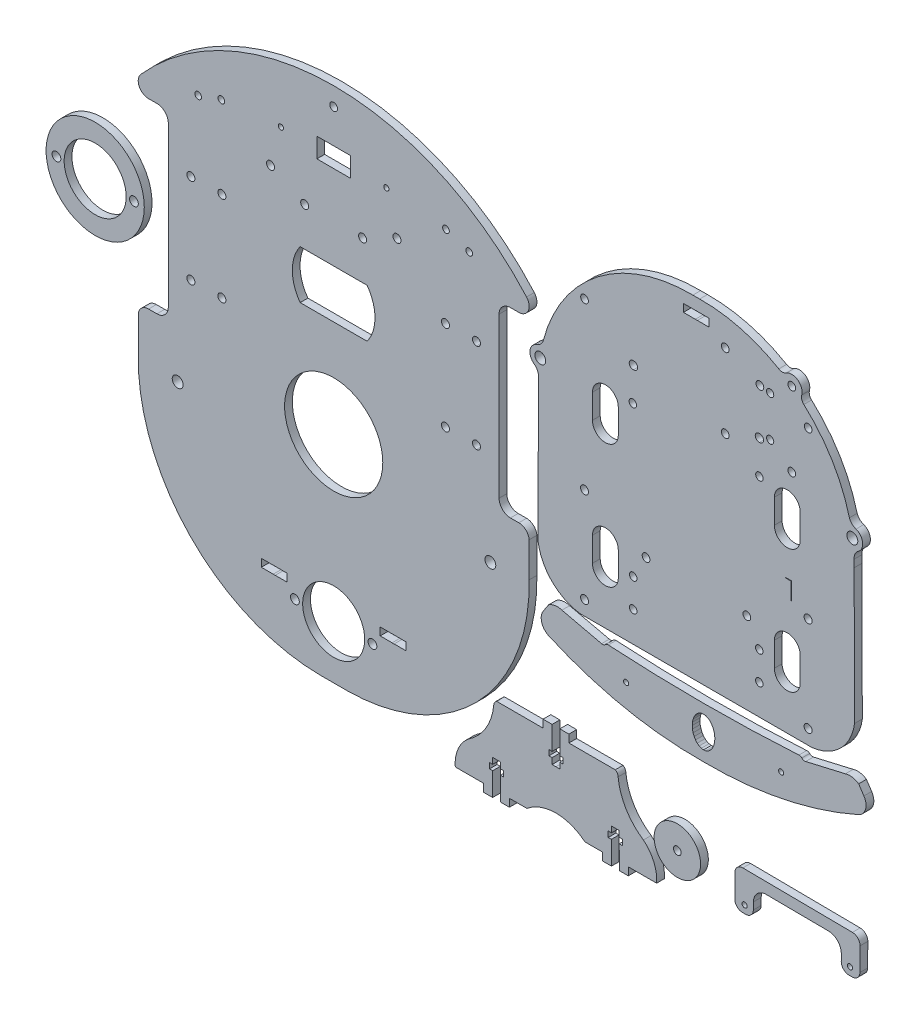
SolidWorks part; units mm, degrees
other "caster_spacer"
other "bottom_plate"
other "top_plate"
other "bumper"
other "rear_upright"
other "bumper_cap"
other "ir_spacer"
material "Perspex (TM) GS Acrylic Cast Sheet"
ref_plane "Front Plane" through (0, 0, 0) normal (0, 0, 1) x (1, 0, 0)
ref_plane "Top Plane" through (0, 0, 0) normal (0, 1, 0) x (1, 0, 0)
ref_plane "Right Plane" through (0, 0, 0) normal (1, 0, 0) x (0, 0, -1)
sketch "Model" plane through (0, 0, 0) normal (0, 0, 1) x (1, 0, 0)
  line L0 (762.453, 185.9302) -> (736.5177, 185.9248)
  line L1 (736.5216, 167.1802) -> (762.4569, 167.1856)
  line L2 (767.5026, 70.9628) -> (767.5026, 73.9628)
  line L3 (767.5026, 73.9628) -> (777.5026, 73.9628)
  line L4 (777.5026, 73.9628) -> (777.5026, 70.9628)
  line L5 (777.5026, 70.9628) -> (767.5026, 70.9628)
  line L6 (731.5026, 70.9628) -> (731.5026, 73.9628)
  line L7 (731.5026, 73.9628) -> (721.5026, 73.9628)
  line L8 (721.5026, 73.9628) -> (721.5026, 70.9628)
  line L9 (721.5026, 70.9628) -> (731.5026, 70.9628)
  line L10 (743.0006, 225.5162) -> (743.0006, 226.1909)
  line L11 (743.0006, 226.1909) -> (756.0006, 226.1909)
  line L12 (756.0006, 226.1909) -> (756.0006, 225.5162)
  line L13 (756.0006, 225.5162) -> (756.0006, 221.5162)
  line L14 (756.0006, 221.5162) -> (756.0006, 218.5909)
  line L15 (756.0006, 218.5909) -> (743.0006, 218.5909)
  line L16 (743.0006, 218.5909) -> (743.0006, 221.5162)
  line L17 (743.0006, 221.5162) -> (743.0006, 225.5162)
  line L105 (749.5032, 246.3817) -> (749.5032, 35.4161) construction
  line L106 (813.5059, 156.7021) -> (813.5059, 140.1083)
  line L107 (813.5059, 185.2021) -> (813.5059, 156.7021)
  line L108 (813.5059, 201.7963) -> (813.5059, 185.2021)
  line L109 (754.7206, 46.1998) -> (749.5032, 46.1998)
  line L110 (825.1364, 131.975) -> (825.1364, 118.5589)
  line L111 (817.9122, 135.7021) -> (821.1397, 135.7021)
  line L112 (821.1479, 206.2021) -> (817.9117, 206.2021)
  line L113 (924.411, 169.0147) -> (924.411, 168.8131)
  line L114 (924.411, 168.8131) -> (926.4659, 168.8131)
  line L115 (926.4659, 168.8131) -> (926.4659, 162.2785)
  line L116 (926.4659, 162.2785) -> (926.6563, 162.2785)
  line L117 (827.0369, 191.9224) -> (827.1534, 191.8384)
  line L118 (952.6204, 191.8939) -> (952.5039, 191.81)
  line L127 (726.5026, 73.9628) -> (726.5026, 70.9628) construction
  line L128 (772.5026, 73.9628) -> (772.5026, 70.9628) construction
  line L129 (889.8411, 241.0646) -> (889.8419, 238.0646)
  line L133 (846.5809, 159.4459) -> (846.5809, 122.7207) construction
  line L134 (933.1077, 159.4459) -> (933.1077, 122.7207) construction
  line L135 (706.237, 188.2998) -> (706.237, 153.5998) construction
  line L140 (677.8584, 206.2021) -> (681.0947, 206.2021)
  line L165 (685.5005, 201.7963) -> (685.5005, 185.2021)
  line L166 (685.5005, 185.2021) -> (685.5005, 156.7021)
  line L167 (685.5005, 156.7021) -> (685.5005, 140.1083)
  line L191 (681.0942, 135.7021) -> (677.8667, 135.7021)
  line L214 (673.87, 131.975) -> (673.87, 118.5589)
  line L215 (744.2858, 46.1998) -> (749.5032, 46.1998)
  line L265 (698.9161, 168.299) -> (701.1615, 168.299)
  line L266 (698.9161, 175.0351) -> (698.9161, 168.299)
  line L267 (743.0006, 221.5162) -> (743.0006, 218.5909)
  line L268 (743.0006, 218.5909) -> (756.0006, 218.5909)
  line L269 (756.0006, 218.5909) -> (756.0006, 221.5162)
  line L270 (756.0006, 225.5162) -> (756.0006, 226.1909)
  line L271 (756.0006, 226.1909) -> (743.0006, 226.1909)
  line L272 (743.0006, 226.1909) -> (743.0006, 225.5162)
  line L273 (894.8419, 238.0659) -> (894.8411, 241.0659)
  line L274 (894.8411, 241.0659) -> (884.8411, 241.0633)
  line L275 (884.8411, 241.0633) -> (884.8419, 238.0633)
  line L276 (884.8419, 238.0633) -> (894.8419, 238.0659)
  line L277 (920.0432, 138.3883) -> (920.0432, 145.7783)
  line L278 (930.0432, 145.7783) -> (930.0432, 138.3883)
  line L279 (930.0432, 138.3883) -> (930.0432, 136.3883)
  line L280 (920.0432, 136.3883) -> (920.0432, 138.3883)
  line L281 (859.6454, 138.3883) -> (859.6454, 145.7783)
  line L282 (849.6454, 145.7783) -> (849.6454, 138.3883)
  line L283 (849.6454, 138.3883) -> (849.6454, 136.3883)
  line L284 (859.6454, 136.3883) -> (859.6454, 138.3883)
  line L285 (859.6454, 186.3144) -> (859.6454, 193.7043)
  line L286 (849.6454, 193.7043) -> (849.6454, 186.3144)
  line L287 (849.6454, 186.3144) -> (849.6454, 184.3144)
  line L288 (859.6454, 184.3144) -> (859.6454, 186.3144)
  line L289 (920.0432, 186.3144) -> (920.0432, 193.7043)
  line L290 (930.0432, 193.7043) -> (930.0432, 186.3144)
  line L291 (930.0432, 186.3144) -> (930.0432, 184.3144)
  line L292 (920.0432, 184.3144) -> (920.0432, 186.3144)
  line L293 (926.6563, 169.0147) -> (924.411, 169.0147)
  line L294 (926.6563, 162.2785) -> (926.6563, 169.0147)
  line L295 (888.5041, 245.6853) -> (891.1289, 245.685)
  line L296 (950.919, 185.4958) -> (951.0795, 133.4118)
  line L297 (934.5559, 117.0935) -> (889.8278, 117.0953)
  line L298 (889.8278, 117.0953) -> (845.0997, 117.0935)
  line L299 (828.5761, 133.4118) -> (828.7367, 185.4958)
  line L304 (954.7025, 110.9038) -> (952.6709, 113.9687)
  line L305 (947.5197, 114.7553) -> (932.1721, 111.2007)
  line L306 (853.1715, 111.1992) -> (837.8238, 114.7532)
  line L307 (832.6726, 113.9664) -> (830.6411, 110.9014)
  line L308 (892.636, 107.3177) -> (891.7828, 107.2027)
  line L309 (891.7828, 107.2027) -> (890.9625, 106.8618)
  line L310 (890.9625, 106.8618) -> (890.2065, 106.3083)
  line L311 (890.2065, 106.3083) -> (889.5438, 105.5633)
  line L312 (889.5438, 105.5633) -> (889, 104.6556)
  line L313 (889, 104.6556) -> (888.5959, 103.6201)
  line L314 (888.5959, 103.6201) -> (888.3471, 102.4964)
  line L315 (888.3471, 102.4964) -> (888.263, 101.3278)
  line L316 (888.263, 101.3278) -> (888.3471, 100.1592)
  line L317 (888.3471, 100.1592) -> (888.5959, 99.0356)
  line L318 (888.5959, 99.0356) -> (889, 98)
  line L319 (889, 98) -> (889.5438, 97.0923)
  line L320 (889.5438, 97.0923) -> (890.2065, 96.3474)
  line L321 (890.2065, 96.3474) -> (890.9625, 95.7939)
  line L322 (890.9625, 95.7939) -> (891.7828, 95.453)
  line L323 (891.7828, 95.453) -> (892.636, 95.3379)
  line L324 (892.636, 95.3379) -> (893.4891, 95.453)
  line L325 (893.4891, 95.453) -> (894.3094, 95.7939)
  line L326 (894.3094, 95.7939) -> (895.0654, 96.3474)
  line L327 (895.0654, 96.3474) -> (895.7281, 97.0923)
  line L328 (895.7281, 97.0923) -> (896.2719, 98)
  line L329 (896.2719, 98) -> (896.676, 99.0356)
  line L330 (896.676, 99.0356) -> (896.9249, 100.1592)
  line L331 (896.9249, 100.1592) -> (897.0089, 101.3278)
  line L332 (897.0089, 101.3278) -> (896.9249, 102.4964)
  line L333 (896.9249, 102.4964) -> (896.676, 103.6201)
  line L334 (896.676, 103.6201) -> (896.2719, 104.6556)
  line L335 (896.2719, 104.6556) -> (895.7281, 105.5633)
  line L336 (895.7281, 105.5633) -> (895.0654, 106.3083)
  line L337 (895.0654, 106.3083) -> (894.3094, 106.8618)
  line L338 (894.3094, 106.8618) -> (893.4891, 107.2027)
  line L339 (893.4891, 107.2027) -> (892.636, 107.3177)
  line L344 (918.4418, 206.5816) -> (860.9418, 206.5816) construction
  line L345 (900.391, 237.0011) -> (927.5576, 237.0011) construction
  line L346 (898.391, 235.0011) -> (898.391, 205.066) construction
  line L347 (914.7643, 201.2678) -> (864.7643, 201.2679)
  line L349 (861.7643, 135.2879) -> (861.7643, 198.2679)
  line L357 (917.7743, 135.2879) -> (861.7643, 135.2879) construction
  line L376 (837.016, 63.4329) -> (837.017, 61.1129)
  line L377 (837.017, 61.1129) -> (835.517, 61.1123)
  line L378 (835.517, 61.1123) -> (834.017, 61.1129)
  line L379 (834.017, 61.1129) -> (834.018, 63.4315)
  line L380 (834.018, 63.4315) -> (832.7679, 63.392)
  line L381 (832.7679, 63.392) -> (832.7689, 65.612)
  line L382 (832.7689, 65.612) -> (834.0188, 65.4755)
  line L383 (834.0188, 65.4755) -> (834.0226, 74.5729)
  line L384 (834.0226, 74.5729) -> (830.5226, 74.5729)
  line L385 (830.5226, 74.5729) -> (830.5226, 71.5729)
  line L386 (830.5226, 71.5729) -> (812.5534, 71.5726)
  line L387 (796.5538, 41.5726) -> (807.517, 41.5726)
  line L388 (807.517, 41.5726) -> (807.517, 38.5451)
  line L389 (807.517, 38.5451) -> (811.0161, 38.5442)
  line L390 (811.0161, 38.5442) -> (811.0201, 47.5416)
  line L391 (811.0201, 47.5416) -> (809.77, 47.5056)
  line L392 (809.77, 47.5056) -> (809.7771, 49.7256)
  line L393 (809.7771, 49.7256) -> (811.0269, 49.6816)
  line L394 (811.0269, 49.6816) -> (811.0343, 52.0016)
  line L395 (811.0343, 52.0016) -> (812.5343, 51.9968)
  line L396 (812.5343, 51.9968) -> (814.0343, 52.0016)
  line L397 (814.0343, 52.0016) -> (814.0417, 49.6816)
  line L398 (814.0417, 49.6816) -> (815.2916, 49.7256)
  line L399 (815.2916, 49.7256) -> (815.2987, 47.5056)
  line L400 (815.2987, 47.5056) -> (814.0485, 47.5416)
  line L401 (814.0485, 47.5416) -> (814.0525, 38.5434)
  line L402 (814.0525, 38.5434) -> (817.517, 38.5425)
  line L403 (817.517, 38.5425) -> (817.5177, 41.5387)
  line L404 (817.5177, 41.5387) -> (824.296, 41.5384)
  line L405 (846.7281, 41.5374) -> (853.5166, 41.5371)
  line L406 (853.5166, 41.5371) -> (853.5174, 38.5409)
  line L407 (853.5174, 38.5409) -> (856.9818, 38.5418)
  line L408 (856.9818, 38.5418) -> (856.9858, 47.54)
  line L409 (856.9858, 47.54) -> (855.7357, 47.504)
  line L410 (855.7357, 47.504) -> (855.7427, 49.724)
  line L411 (855.7427, 49.724) -> (856.9926, 49.68)
  line L412 (856.9926, 49.68) -> (857, 52)
  line L413 (857, 52) -> (858.5, 51.9952)
  line L414 (858.5, 51.9952) -> (860, 52)
  line L415 (860, 52) -> (860.0074, 49.68)
  line L416 (860.0074, 49.68) -> (861.2572, 49.724)
  line L417 (861.2572, 49.724) -> (861.2643, 47.504)
  line L418 (861.2643, 47.504) -> (860.0142, 47.54)
  line L419 (860.0142, 47.54) -> (860.0182, 38.5426)
  line L420 (860.0182, 38.5426) -> (863.5174, 38.544)
  line L421 (863.5174, 38.544) -> (863.5166, 41.5726)
  line L422 (863.5166, 41.5726) -> (874.4802, 41.5726)
  line L423 (858.4802, 71.5726) -> (840.5226, 71.5729)
  line L424 (840.5226, 71.5729) -> (840.5226, 74.5729)
  line L425 (840.5226, 74.5729) -> (837.0113, 74.5729)
  line L426 (837.0113, 74.5729) -> (837.0151, 65.4769)
  line L427 (837.0151, 65.4769) -> (838.265, 65.6134)
  line L428 (838.265, 65.6134) -> (838.266, 63.3934)
  line L429 (838.266, 63.3934) -> (837.016, 63.4329)
  line L430 (953.2111, 59.9452) -> (953.1264, 50.9456)
  line L431 (950.0983, 47.9739) -> (948.8984, 47.9852)
  line L432 (945.9267, 51.0133) -> (945.9441, 53.7658)
  line L433 (940.9847, 58.806) -> (916.9817, 59)
  line L434 (911.9414, 54.0406) -> (911.9182, 51.3331)
  line L435 (908.8901, 48.3615) -> (907.6902, 48.3727)
  line L436 (904.7185, 51.4008) -> (904.8032, 60.4004)
  line L437 (907.8312, 63.3721) -> (915.1688, 63.3031)
  line L438 (915.1688, 63.3031) -> (924.0406, 63.2196)
  line L439 (924.0406, 63.2196) -> (950.2394, 62.9733)
  line L442 (917.7943, 198.3279) -> (917.7743, 135.2879)
  line L443 (900.391, 203.066) -> (927.5576, 203.066) construction
  line L444 (929.5576, 235.0011) -> (929.5576, 205.066) construction
  line L445 (918.4418, 133.5816) -> (904.471, 133.5816) construction
  line L446 (918.4418, 133.5816) -> (918.4418, 214.5816) construction
  line L447 (918.4418, 214.5816) -> (860.9418, 214.5816) construction
  line L448 (860.9418, 133.5816) -> (860.9418, 214.5816) construction
  line L449 (902.2425, 131.0816) -> (865.8804, 131.0816) construction
  line L450 (865.8804, 131.0816) -> (863.8094, 133.5816) construction
  line L451 (902.2425, 131.0816) -> (904.471, 133.5816) construction
  line L452 (863.8094, 133.5816) -> (860.9418, 133.5816) construction
  line L453 (912.7643, 210.6675) -> (912.6437, 210.6675) construction
  circle A0 centre (729.0806, 222.3009) radius 1
  circle A1 centre (694.237, 153.5998) radius 1.55
  arc A2 (762.4569, 167.1856) -> (762.453, 185.9302) centre (749.4873, 176.5552) ccw
  arc A3 (736.5177, 185.9248) -> (736.5216, 167.1802) centre (749.4873, 176.5552) ccw
  circle A4 centre (804.7638, 188.2998) radius 1.55
  circle A5 centre (804.7638, 153.5998) radius 1.55
  circle A6 centre (706.0417, 219.9275) radius 1.3
  circle A7 centre (694.237, 188.2998) radius 1.55
  circle A8 centre (810.1315, 116.936) radius 2.1
  circle A10 centre (749.5004, 239.3077) radius 1.5
  circle A11 centre (706.237, 153.5998) radius 1.55
  circle A12 centre (749.5028, 66.7627) radius 12
  circle A13 centre (792.7638, 153.5998) radius 1.55
  circle A14 centre (706.237, 188.2998) radius 1.55
  circle A15 centre (764.5026, 66.7627) radius 1.7
  circle A17 centre (769.8906, 222.3009) radius 1
  circle A19 centre (738.2854, 200.9472) radius 1.55
  circle A20 centre (689.1201, 116.936) radius 2.1
  circle A21 centre (749.5, 129.5) radius 19
  arc A22 (673.87, 118.5589) -> (744.2858, 46.1998) centre (744.783, 117.1256) ccw
  circle A24 centre (889.8415, 239.5646) radius 1.55
  circle A25 centre (734.5029, 66.7627) radius 1.7
  circle A26 centre (792.7638, 188.2998) radius 1.55
  circle A27 centre (697.0541, 216.8624) radius 1.3
  circle A28 centre (725.0701, 207.4516) radius 1.55
  circle A29 centre (760.6854, 200.9472) radius 1.55
  arc A30 (813.5059, 140.1083) -> (817.9122, 135.7021) centre (817.9122, 140.1083) ccw
  circle A31 centre (773.998, 207.4516) radius 1.55
  circle A32 centre (918.4131, 212.1419) radius 1.4001
  arc A34 (930.0432, 145.7783) -> (920.0432, 145.7783) centre (925.0432, 145.7783) ccw
  arc A35 (920.0432, 136.3883) -> (930.0432, 136.3883) centre (925.0432, 136.3883) ccw
  arc A36 (859.6454, 145.7783) -> (849.6454, 145.7783) centre (854.6454, 145.7783) ccw
  arc A37 (849.6454, 136.3883) -> (859.6454, 136.3883) centre (854.6454, 136.3883) ccw
  circle A41 centre (933.1077, 122.7207) radius 1.55
  circle A42 centre (901.0379, 205.4969) radius 1.5
  circle A44 centre (933.1077, 159.4459) radius 1.55
  circle A45 centre (829.4641, 195.0945) radius 2.1
  circle A46 centre (846.5809, 122.7207) radius 1.55
  circle A47 centre (846.5809, 159.4459) radius 1.55
  circle A48 centre (926.7879, 205.4969) radius 1.5
  arc A49 (859.6454, 193.7043) -> (849.6454, 193.7043) centre (854.6454, 193.7043) ccw
  arc A50 (849.6454, 184.3144) -> (859.6454, 184.3144) centre (854.6454, 184.3144) ccw
  arc A52 (930.0432, 193.7043) -> (920.0432, 193.7043) centre (925.0432, 193.7043) ccw
  arc A53 (920.0432, 184.3144) -> (930.0432, 184.3144) centre (925.0432, 184.3144) ccw
  circle A54 centre (950.2253, 195.0945) radius 2.1
  circle A57 centre (846.5809, 223.4459) radius 1.5
  circle A58 centre (933.1077, 223.4459) radius 1.5
  circle A59 centre (901.0379, 234.2969) radius 1.5
  arc A61 (865.5084, 212.1615) -> (865.5098, 209.1736) centre (865.3745, 210.6675) ccw
  arc A63 (828.0192, 198.8659) -> (827.0369, 191.9224) centre (829.434, 195.1245) ccw
  arc A64 (828.0192, 198.8659) -> (830.5855, 201.3861) centre (826.7989, 202.6753) ccw
  arc A65 (930.6261, 233.2652) -> (924.6454, 237.6444) centre (926.7879, 234.2969) ccw
  arc A66 (921.7667, 237.5881) -> (924.6454, 237.6444) centre (923.1601, 239.9649) ccw
  arc A67 (921.7667, 237.5881) -> (891.1289, 245.685) centre (891.9253, 186.6847) ccw
  arc A68 (930.6261, 233.2652) -> (931.4417, 230.5039) centre (933.2868, 232.55) ccw
  circle A70 centre (792.9512, 219.9275) radius 1.3
  arc A71 (929.5576, 235.0011) -> (927.5576, 237.0011) centre (927.5576, 235.0011) ccw construction
  arc A73 (929.5576, 205.066) -> (927.5576, 203.066) centre (927.5576, 205.066) cw construction
  circle A76 centre (909.3945, 148.665) radius 1.5
  circle A78 centre (926.7879, 234.2969) radius 1.5
  arc A79 (888.5041, 245.6853) -> (830.5855, 201.3861) centre (887.7304, 186.6847) ccw
  arc A80 (949.0811, 201.3434) -> (931.4417, 230.5039) centre (891.9253, 186.6847) ccw
  arc A81 (949.0811, 201.3434) -> (951.641, 198.8379) centre (952.8629, 202.6467) ccw
  arc A82 (952.6204, 191.8939) -> (951.641, 198.8379) centre (950.2246, 195.097) ccw
  arc A83 (952.5039, 191.81) -> (950.9058, 188.3851) centre (954.8997, 188.6068) ccw
  arc A84 (950.919, 185.4958) -> (950.9058, 188.3851) centre (893.0035, 186.6772) ccw
  arc A85 (934.5559, 117.0935) -> (951.0795, 133.4118) centre (932.3736, 135.8281) ccw
  arc A86 (828.5761, 133.4118) -> (845.0997, 117.0935) centre (847.282, 135.8281) ccw
  arc A87 (828.75, 188.4128) -> (828.7367, 185.4958) centre (899.6309, 186.6303) ccw
  arc A88 (828.75, 188.4128) -> (827.1534, 191.8384) centre (824.7562, 188.6362) ccw
  arc A89 (900.391, 203.066) -> (898.391, 205.066) centre (900.391, 205.066) cw construction
  arc A90 (898.391, 235.0011) -> (900.391, 237.0011) centre (900.391, 235.0011) cw construction
  circle A94 centre (862.6683, 102.9568) radius 1
  circle A95 centre (922.6754, 102.9568) radius 1
  arc A96 (832.7255, 103.5937) -> (892.6722, 91.3117) centre (890.6838, 234.0438) ccw
  arc A97 (892.6722, 91.3117) -> (952.6184, 103.596) centre (894.655, 234.0439) ccw
  arc A98 (952.6184, 103.596) -> (954.7025, 110.9038) centre (950.535, 108.1413) ccw
  arc A99 (952.6709, 113.9687) -> (947.5197, 114.7553) centre (949.3098, 109.2178) ccw
  arc A100 (930.6861, 111.651) -> (932.1721, 111.2007) centre (931.8013, 112.6541) ccw
  arc A101 (930.6861, 111.651) -> (929.5576, 112.0619) centre (929.6871, 110.6626) ccw
  arc A102 (855.7695, 112.0619) -> (929.5576, 112.0619) centre (892.6636, 719.0984) ccw
  arc A103 (855.7695, 112.0619) -> (854.6575, 111.6496) centre (855.6565, 110.6612) ccw
  arc A104 (853.1715, 111.1992) -> (854.6575, 111.6496) centre (853.5422, 112.6526) ccw
  arc A105 (837.8238, 114.7532) -> (832.6726, 113.9664) centre (836.0339, 109.2156) ccw
  arc A106 (830.6411, 110.9014) -> (832.7255, 103.5937) centre (834.8087, 108.1391) ccw
  circle A108 centre (801.9388, 216.8624) radius 1.3
  circle A110 centre (726.5026, 72.4628) radius 1.55
  circle A111 centre (772.5026, 72.4628) radius 1.55
  arc A120 (812.5534, 71.5726) -> (811.4511, 69.7327) centre (813.7636, 69.5974) ccw
  arc A121 (801.6888, 53.506) -> (811.4511, 69.7327) centre (789.5148, 71.88) ccw
  arc A122 (801.6888, 53.506) -> (796.5538, 41.5726) centre (810.4709, 42.6555) ccw
  arc A123 (835.517, 45.6303) -> (824.296, 41.5384) centre (835.7261, 27.6255) ccw
  arc A124 (846.7281, 41.5374) -> (835.517, 45.6303) centre (835.319, 27.6868) ccw
  arc A125 (874.4802, 41.5726) -> (869.3451, 53.506) centre (860.563, 42.6555) ccw
  arc A126 (859.5825, 69.7494) -> (869.3451, 53.506) centre (881.5145, 71.8755) ccw
  arc A127 (859.5825, 69.7494) -> (858.4802, 71.5726) centre (857.2667, 69.5942) ccw
  circle A128 centre (949.3266, 50.9813) radius 1
  circle A129 centre (908.5179, 51.3111) radius 1
  arc A130 (953.2111, 59.9452) -> (950.2394, 62.9733) centre (950.2112, 59.9734) ccw
  arc A131 (950.0983, 47.9739) -> (953.1264, 50.9456) centre (950.1266, 50.9738) ccw
  arc A132 (945.9267, 51.0133) -> (948.8984, 47.9852) centre (948.9266, 50.9851) ccw
  arc A133 (945.9441, 53.7658) -> (940.9847, 58.806) centre (940.9443, 53.8062) ccw
  arc A134 (916.9817, 59) -> (911.9414, 54.0406) centre (916.9412, 54.0002) ccw
  arc A135 (908.8901, 48.3615) -> (911.9182, 51.3331) centre (908.9183, 51.3613) ccw
  arc A136 (904.7185, 51.4008) -> (907.6902, 48.3727) centre (907.7184, 51.3726) ccw
  arc A137 (907.8312, 63.3721) -> (904.8032, 60.4004) centre (907.803, 60.3722) ccw
  circle A148 centre (882.5, 56.5) radius 9
  circle A149 centre (882.5, 56.5) radius 1.5
  arc A150 (674.8674, 212.862) -> (677.8584, 206.2021) centre (677.8584, 210.2037) ccw
  arc A151 (681.0947, 206.2021) -> (685.5005, 201.7963) centre (681.0947, 201.7963) cw
  arc A152 (685.5005, 140.1083) -> (681.0942, 135.7021) centre (681.0942, 140.1083) cw
  arc A153 (677.8667, 135.7021) -> (673.87, 131.975) centre (677.8667, 131.6956) ccw
  arc A154 (674.8674, 212.862) -> (824.139, 212.862) centre (749.5032, 146.529) cw
  arc A155 (817.9117, 206.2021) -> (813.5059, 201.7963) centre (817.9117, 201.7963) ccw
  circle A156 centre (804.7694, 188.2998) radius 1.55
  circle A157 centre (804.7694, 153.5998) radius 1.55
  arc A158 (825.1364, 118.5589) -> (754.7206, 46.1998) centre (754.2234, 117.1256) cw
  arc A159 (821.1397, 135.7021) -> (825.1364, 131.975) centre (821.1397, 131.6956) cw
  arc A160 (824.139, 212.862) -> (821.1479, 206.2021) centre (821.1479, 210.2037) cw
  circle A161 centre (657.2032, 168.9811) radius 12
  circle A162 centre (672.2031, 168.9811) radius 1.7
  circle A163 centre (657.2032, 168.9811) radius 19
  circle A164 centre (642.2034, 168.9811) radius 1.7
  arc A182 (914.2583, 209.172) -> (914.2599, 212.1631) centre (914.3745, 210.6675) ccw
  circle A184 centre (870.3945, 148.665) radius 1.5
  arc A185 (865.5098, 209.1736) -> (865.5084, 212.1615) centre (865.6437, 210.6676) ccw
  arc A186 (914.2599, 212.1631) -> (914.2583, 209.172) centre (914.1437, 210.6676) ccw
  arc A192 (864.7643, 201.2679) -> (861.7643, 198.2679) centre (864.7643, 198.2679) ccw
  arc A193 (917.7943, 198.3279) -> (914.7643, 201.2678) centre (914.8093, 198.2829) ccw
  circle A194 centre (914.2643, 197.7679) radius 1.45
  circle A195 centre (865.4143, 128.8179) radius 1.45
  circle A196 centre (865.2643, 197.8179) radius 1.45
  circle A197 centre (914.2143, 128.7679) radius 1.45
  circle A202 centre (865.4143, 139.8179) radius 1.45
  circle A203 centre (914.2143, 139.7679) radius 1.45
  circle A204 centre (918.4132, 227.8096) radius 1.3995
  circle A259 centre (914.4452, 228.3511) radius 1.5004
  point P19 (846.5809, 141.0833)
  point P38 (933.1077, 141.0833)
  point P91 (926.7879, 234.2969)
  dimension "D1" = 2
extrude "Boss-Extrude1" add sketch "Model" along normal blind 3
other "Save Bodies1"
